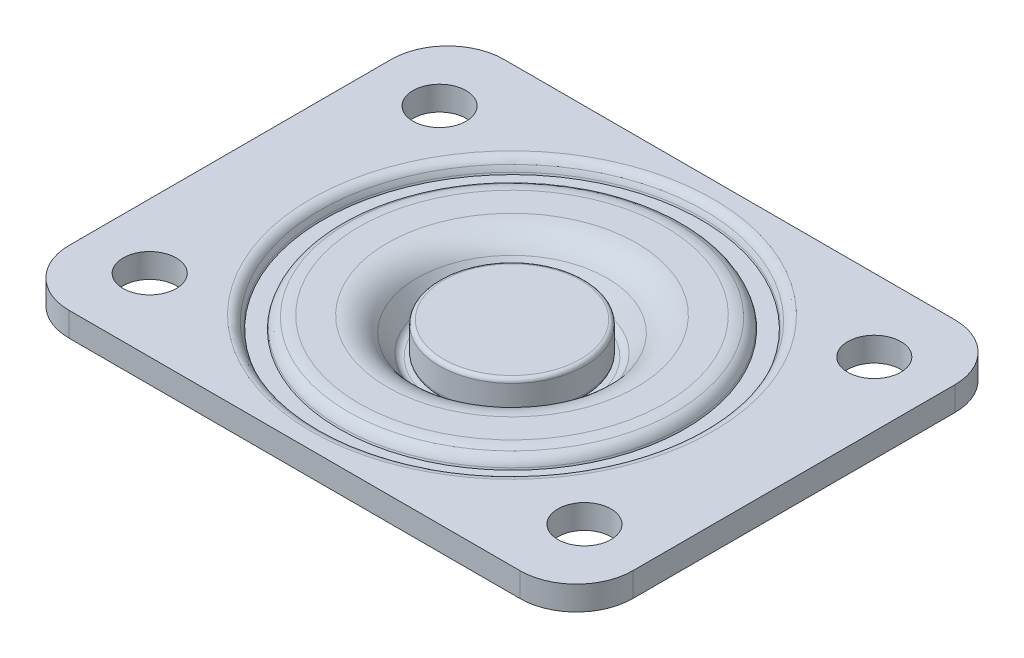
SolidWorks part; units mm, degrees
ref_plane "Front Plane" through (0, 0, 0) normal (0, 0, 1) x (1, 0, 0)
ref_plane "Top Plane" through (0, 0, 0) normal (0, 1, 0) x (1, 0, 0)
ref_plane "Right Plane" through (0, 0, 0) normal (1, 0, 0) x (0, 0, -1)
ref_axis "Axis_X" through (-38.5, 0, 0) along (1, 0, 0)
ref_axis "Axis_Y" through (0, 3.925, 0) along (0, -1, 0)
ref_axis "Axis_Z" through (0, 0, -29.7) along (0, 0, 1)
sketch "Sketch1" plane through (0, 0, 0) normal (0, 1, 0) x (1, 0, 0)
  line L1 (-35, -27) -> (35, -27)
  line L2 (-35, -27) -> (-35, 27)
  line L3 (-35, 27) -> (35, 27)
  line L4 (35, -27) -> (35, 27)
  line L5 (-35, -27) -> (35, 27) construction
  line L6 (-35, 27) -> (35, -27) construction
  point P0 (0, 0)
  dimension "MSM_31" = 54
  dimension "MSM_32" = 70
extrude "Boss-Extrude1" add sketch "Sketch1" along normal blind 3
sketch "Sketch2" plane through (0, 0, 0) normal (0, 0, 1) x (1, 0, 0)
  line L0 (-14.75, 0) -> (-11.5991, -4.5)
  line L1 (-35, 0) -> (35, 0) construction
  line L2 (-11.5991, -4.5) -> (-5, -4.5)
  line L3 (-5, -4.5) -> (-5, -15.5)
  line L4 (-5, -15.5) -> (0, -15.5)
  line L5 (-14.75, 0) -> (0, 0)
  line L6 (0, -15.5) -> (0, 0) construction
  line L7 (0, 0) -> (0, -15.5)
  dimension "MSM_35" = 10
  dimension "MSM_34" = 15.5
  dimension "MSM_33" = 4.5
  dimension "MSM_36" = 125
  dimension "MSM_37" = 29.5
revolve "Revolve1" add sketch "Sketch2" angle 360 about L6
fillet "Fillet1" radius 4 1 edges at (0, -4.5, -11.5991)
fillet "Fillet2" radius 1.5 1 edges at (0, 0, -14.75)
fillet "Fillet3" radius 7 4 edges at (35, 1.5, -27) (35, 1.5, 27) (-35, 1.5, -27) (-35, 1.5, 27)
sketch "Sketch3" plane through (0, 0, 0) normal (1, 0, 0) x (0, 0, -1)
  line L0 (20.29, 0) -> (20.5022, -0.3675)
  line L1 (24.75, 0) -> (24.5378, -0.3675)
  line L2 (0, -15.5) -> (0, 0) construction
  line L4 (-5, -15.5) -> (5, -15.5) construction
  line L5 (20.29, 0) -> (24.75, 0)
  line L6 (-20, 0) -> (20, 0) construction
  arc A0 (20.5022, -0.3675) -> (24.5378, -0.3675) centre (22.52, 0.7975) ccw
  dimension "FIX_6" = 2.33
  dimension "FIX_2" = 60
  dimension "FIX_3" = 60
  dimension "FIX_4" = 40.58
  dimension "FIX_5" = 49.5
revolve "Revolve2" add sketch "Sketch3" angle 360 about axis through (0, 3.925, 0) along (0, -1, 0)
sketch "Sketch4" plane through (0, 0, 0) normal (1, 0, 0) x (0, 0, -1)
  line L0 (0, 0) -> (0, -15.5) construction
  line L2 (-5, -15.5) -> (5, -15.5) construction
  line L3 (0, 3) -> (0, 2.5)
  line L4 (-20, 3) -> (20, 3) construction
  line L5 (0, 2.5) -> (9, 2.5)
  line L6 (9, 2.5) -> (9, -1)
  line L7 (8.5, -1.5) -> (9.9991, -1.5)
  line L8 (9.9991, -1.5) -> (13.15, 3)
  line L9 (13.15, 3) -> (0, 3)
  arc A0 (8.5, -1.5) -> (9, -1) centre (8.5, -1) ccw
  dimension "FIX_13" = 0.5
  dimension "FIX_8" = 0.5
  dimension "FIX_9" = 4.5
  dimension "FIX_10" = 18
  dimension "FIX_11" = 26.3
  dimension "FIX_12" = 125
revolve "Cut-Revolve1" cut sketch "Sketch4" angle 360 about axis through (0, 3.925, 0) along (0, -1, 0)
sketch "Sketch5" plane through (0, 0, 0) normal (1, 0, 0) x (0, 0, -1)
  line L0 (21.4133, 1.7054) -> (21.488, 1.5)
  line L1 (21.488, 1.5) -> (23.488, 1.5)
  line L2 (23.488, 1.5) -> (23.562, 1.7033)
  line L3 (-20, 3) -> (20, 3) construction
  line L4 (0, 0) -> (0, -15.5) construction
  line L5 (-5, -15.5) -> (5, -15.5) construction
  line L6 (27, 3) -> (20, 3) construction
  line L7 (18.9997, 3) -> (24.9873, 3)
  arc A0 (21.4133, 1.7054) -> (20.3455, 2.7668) centre (19.75, 1.1) ccw
  arc A1 (20.3455, 2.7668) -> (18.9997, 3) centre (18.9997, -1) ccw
  arc A2 (23.8564, 2.3411) -> (23.562, 1.7033) centre (27.5275, 0.26) ccw
  arc A3 (24.9873, 3) -> (23.8564, 2.3411) centre (24.9873, 1.7) ccw
  dimension "FIX_22" = 4
  dimension "FIX_23" = 1.77
  dimension "FIX_26" = 1.3
  dimension "FIX_27" = 4.22
  dimension "FIX_15" = 2
  dimension "FIX_16" = 1.9
  dimension "FIX_17" = 4
  dimension "FIX_18" = 39.5
  dimension "FIX_19" = 110
  dimension "FIX_20" = 110
  dimension "FIX_21" = 1.5
  dimension "FIX_24" = 2.74
  dimension "FIX_25" = 1.3
revolve "Cut-Revolve2" cut sketch "Sketch5" angle 360 about axis through (0, 3.925, 0) along (0, -1, 0)
sketch "Sketch6" plane through (0, 3, 0) normal (0, 1, 0) x (1, 0, 0)
  line L0 (0, 0) -> (-35, 0) construction
  line L1 (-35, 20) -> (-35, -20) construction
  line L2 (0, 0) -> (0, 27) construction
  line L3 (28, 27) -> (-28, 27) construction
  circle A0 centre (-27, 18) radius 3.3
  circle A1 centre (27, 18) radius 3.3
  circle A2 centre (27, -18) radius 3.3
  circle A3 centre (-27, -18) radius 3.3
  dimension "FIX_31" = 6.6
  dimension "FIX_29" = 36
  dimension "FIX_30" = 54
extrude "Cut-Extrude1" cut sketch "Sketch6" against normal through all
fillet "Fillet4" radius 4.5 1 edges at (0, 3, 13.15)
fillet "Fillet5" radius 1 1 edges at (0, -1.5, 9.9991)
fillet "Fillet6" radius 0.5 3 edges at (0, 2.5, 9) (0, 0, 20.29) (0, 0, 24.75)
sketch "Sketch7" plane through (0, 0, 0) normal (1, 0, 0) x (0, 0, -1)
  line L0 (0, 0) -> (0, -15.5) construction
  line L2 (-5, -15.5) -> (5, -15.5) construction
  line L3 (0, 3) -> (0, 1.6435)
  line L4 (-20, 3) -> (20, 3) construction
  line L5 (0, 1.6435) -> (8, 1.6435)
  line L6 (0, 3) -> (16.18, 3)
  line L7 (16.18, 3) -> (10.0081, -4.1)
  line L8 (10.0081, -4.1) -> (9.0019, -4.1)
  line L9 (27, 3) -> (20, 3) construction
  arc A0 (9.0019, -4.1) -> (8, 1.6435) centre (6.37, -1.6) ccw
  dimension "FIX_37" = 7.26
  dimension "FIX_35" = 12.74
  dimension "FIX_36" = 4.6
  dimension "FIX_38" = 131
  dimension "FIX_39" = 7.1
  dimension "FIX_40" = 32.36
  dimension "FIX_41" = 16
revolve "Cut-Revolve3" [suppressed] cut sketch "Sketch7" angle 360 about axis through (0, 3.925, 0) along (0, -1, 0)
sketch "Sketch8" [suppressed] plane through (0, 3, 0) normal (0, 1, 0) x (1, 0, 0)
  line L0 (35.7, 22.25) -> (38.9, 22.25) construction
  line L1 (35.7, 26.5) -> (38.9, 26.5)
  line L2 (35.7, 18) -> (38.9, 18)
  line L3 (35.7, -22.25) -> (38.9, -22.25) construction
  line L4 (35.7, -18) -> (38.9, -18)
  line L5 (35.7, -26.5) -> (38.9, -26.5)
  line L6 (-38.9, 22.25) -> (-35.7, 22.25) construction
  line L7 (-38.9, 26.5) -> (-35.7, 26.5)
  line L8 (-38.9, 18) -> (-35.7, 18)
  line L9 (-38.9, -22.25) -> (-35.7, -22.25) construction
  line L10 (-38.9, -18) -> (-35.7, -18)
  line L11 (-38.9, -26.5) -> (-35.7, -26.5)
  line L12 (0, 0) -> (35, 0) construction
  line L13 (35, -20) -> (35, 20) construction
  line L15 (28, 27) -> (-28, 27) construction
  line L16 (0, 27) -> (0, 0) construction
  arc A0 (35.7, 26.5) -> (35.7, 18) centre (35.7, 22.25) ccw
  arc A1 (38.9, 18) -> (38.9, 26.5) centre (38.9, 22.25) ccw
  arc A2 (35.7, -18) -> (35.7, -26.5) centre (35.7, -22.25) ccw
  arc A3 (38.9, -26.5) -> (38.9, -18) centre (38.9, -22.25) ccw
  arc A4 (-38.9, 26.5) -> (-38.9, 18) centre (-38.9, 22.25) ccw
  arc A5 (-35.7, 18) -> (-35.7, 26.5) centre (-35.7, 22.25) ccw
  arc A6 (-38.9, -18) -> (-38.9, -26.5) centre (-38.9, -22.25) ccw
  arc A7 (-35.7, -26.5) -> (-35.7, -18) centre (-35.7, -22.25) ccw
  point P2 (37.3, 22.25)
  point P7 (37.3, -22.25)
  point P14 (-37.3, 22.25)
  point P21 (-37.3, -22.25)
  dimension "FIX_43" = 8.5
  dimension "FIX_44" = 44.5
  dimension "FIX_45" = 71.4
  dimension "FIX_46" = 77.8
extrude "Cut-Extrude2" [suppressed] cut sketch "Sketch8" against normal through all
fillet "Fillet7" [suppressed] radius 5
fillet "Fillet8" [suppressed] radius 1
equation "\"Factor\"= 1.082532"
